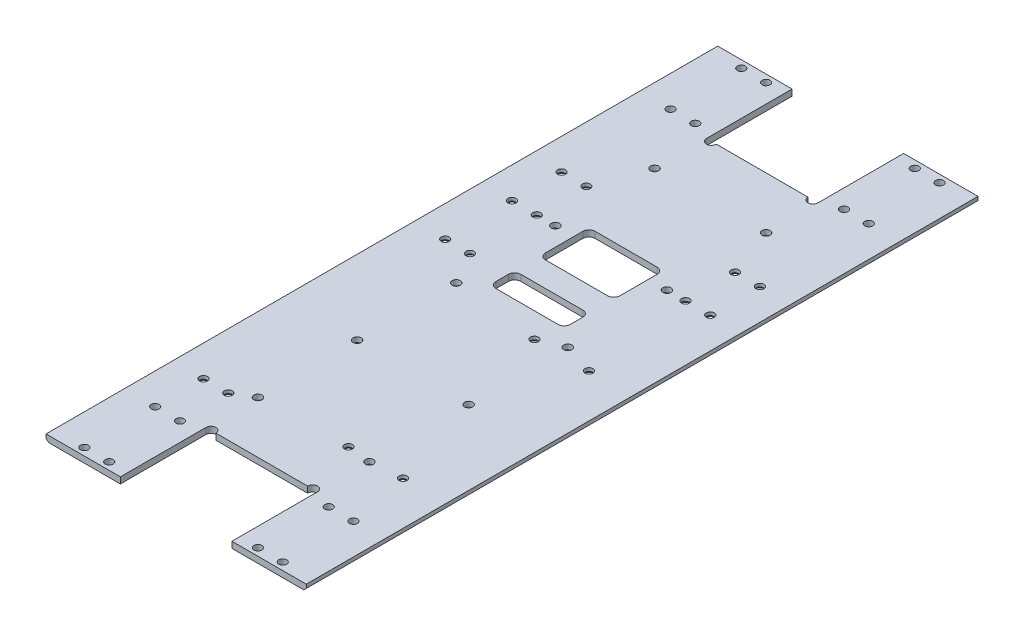
SolidWorks part; units mm, degrees
ref_plane "前视基准面" through (0, 0, 0) normal (0, 0, 1) x (1, 0, 0)
ref_plane "上视基准面" through (0, 0, 0) normal (0, 1, 0) x (1, 0, 0)
ref_plane "右视基准面" through (0, 0, 0) normal (1, 0, 0) x (0, 0, -1)
sketch "草图1" plane through (0, 0, 0) normal (0, 1, 0) x (1, 0, 0)
  line L6 (-52.5, -135.5) -> (52.5, -135.5)
  line L7 (52.5, -135.5) -> (52.5, 135.5)
  line L8 (-52.5, 135.5) -> (52.5, 135.5)
  line L9 (-52.5, -135.5) -> (-52.5, 135.5)
  point P8 (-50, 0)
extrude "凸台-拉伸1" add sketch "草图1" along normal blind 2.5
sketch "草图2" plane through (0, 2.5, 0) normal (0, 1, 0) x (1, 0, 0)
  circle A20 centre (13, -3.95) radius 1.6
  circle A21 centre (35, -3.95) radius 1.6
  circle A24 centre (35, -78.95) radius 1.6
  circle A25 centre (13, -78.95) radius 1.6
extrude "切除-拉伸1" cut sketch "草图2" against normal blind 10
chamfer "倒角4" distance 1 angle 45 2 edges at (52.5, 0, 0) (-52.5, 0, 0)
sketch "草图3" plane through (0, 0, 0) normal (0, -1, 0) x (1, 0, 0)
  line L0 (-22.5, 100.95) -> (22.5, 100.95)
  line L2 (-51.5, 135.5) -> (51.5, 135.5) construction
  line L3 (1.375, 0) -> (-1.375, 0) construction
  line L4 (22.5, 100.95) -> (22.5, 135.5)
  line L5 (22.5, 135.5) -> (-22.5, 135.5)
  line L6 (-22.5, 135.5) -> (-22.5, 100.95)
  line L7 (-22.5, -135.5) -> (-22.5, -100.95)
  line L8 (22.5, -135.5) -> (-22.5, -135.5)
  line L9 (22.5, -100.95) -> (22.5, -135.5)
  line L10 (-22.5, -100.95) -> (22.5, -100.95)
extrude "切除-拉伸2" cut sketch "草图3" against normal blind 10
sketch "草图4" plane through (0, 0, 0) normal (0, -1, 0) x (1, 0, 0)
  line L0 (0, -1.375) -> (0, 1.375) construction
  line L1 (22.5, -100.95) -> (-22.5, -100.95) construction
  line L2 (1.375, 0) -> (-1.375, 0) construction
  circle A0 centre (20.5, -100.95) radius 2
  circle A1 centre (-20.5, -100.95) radius 2
  circle A2 centre (-20.5, 100.95) radius 2
  circle A3 centre (20.5, 100.95) radius 2
extrude "切除-拉伸3" cut sketch "草图4" against normal blind 10
sketch "草图5" plane through (0, 2.5, 0) normal (0, 1, 0) x (1, 0, 0)
  line L0 (0, -1.375) -> (0, 1.375) construction
  line L3 (-1.375, 0) -> (1.375, 0) construction
  circle A0 centre (-40, 103.95) radius 1.6
  circle A1 centre (-30, 103.95) radius 1.6
  circle A4 centre (-40, 132.5) radius 1.6
  circle A5 centre (-30, 132.5) radius 1.6
  circle A6 centre (30, 132.5) radius 1.6
  circle A7 centre (40, 132.5) radius 1.6
  circle A8 centre (30, 103.95) radius 1.6
  circle A9 centre (40, 103.95) radius 1.6
  circle A10 centre (40, -103.95) radius 1.6
  circle A11 centre (30, -103.95) radius 1.6
  circle A12 centre (40, -132.5) radius 1.6
  circle A13 centre (30, -132.5) radius 1.6
  circle A14 centre (-30, -132.5) radius 1.6
  circle A15 centre (-40, -132.5) radius 1.6
  circle A16 centre (-30, -103.95) radius 1.6
  circle A17 centre (-40, -103.95) radius 1.6
extrude "切除-拉伸4" cut sketch "草图5" against normal blind 10
sketch "草图6" plane through (0, 2.5, 0) normal (0, 1, 0) x (1, 0, 0)
  line L0 (0, -1.375) -> (0, 1.375) construction
  circle A0 centre (40, 60) radius 1.6
  circle A1 centre (30, 60) radius 1.6
  circle A2 centre (40, 40) radius 1.6
  circle A3 centre (30, 40) radius 1.6
  circle A4 centre (-30, 40) radius 1.6
  circle A5 centre (-40, 40) radius 1.6
  circle A6 centre (-30, 60) radius 1.6
  circle A7 centre (-40, 60) radius 1.6
  circle A8 centre (-30, -84.45) radius 1.6
  circle A9 centre (-40, -84.45) radius 1.6
  circle A10 centre (-30, 13.05) radius 1.6
  circle A11 centre (-40, 13.05) radius 1.6
  dimension "D1" = 2
extrude "切除-拉伸5" cut sketch "草图6" against normal blind 10
sketch "草图7" plane through (0, 2.5, 0) normal (0, 1, 0) x (1, 0, 0)
  line L0 (0, -1.375) -> (0, 1.375) construction
  line L2 (-1.375, 0) -> (1.375, 0) construction
  circle A0 centre (-22.5, 0) radius 1.65
  circle A2 centre (-22.5, -40) radius 1.65
  circle A4 centre (-22.5, -80) radius 1.65
  circle A5 centre (-22.5, -20) radius 1.65 [skipped]
  circle A6 centre (-22.5, -60) radius 1.65 [skipped]
  circle A7 centre (22.5, -80) radius 1.65
  circle A8 centre (22.5, -40) radius 1.65
  circle A9 centre (22.5, 0) radius 1.65
  circle A10 centre (22.5, 40) radius 1.65
  circle A11 centre (22.5, 80) radius 1.65
  circle A12 centre (-22.5, 80) radius 1.65
  circle A13 centre (-22.5, 40) radius 1.65
  dimension "D1" = 5
extrude "切除-拉伸6" cut sketch "草图7" against normal blind 2
sketch "草图8" plane through (0, 2.5, 0) normal (0, 1, 0) x (1, 0, 0)
  line L0 (0, -1.375) -> (0, 1.375) construction
  circle A0 centre (-22.5, 80) radius 1.55
  circle A1 centre (-22.5, 40) radius 1.55
  circle A2 centre (-22.5, 0) radius 1.55
  circle A3 centre (-22.5, -40) radius 1.55
  circle A4 centre (-22.5, -80) radius 1.55
  circle A5 centre (22.5, -80) radius 1.55
  circle A6 centre (22.5, -40) radius 1.55
  circle A7 centre (22.5, 0) radius 1.55
  circle A8 centre (22.5, 40) radius 1.55
  circle A9 centre (22.5, 80) radius 1.55
  dimension "D1" = 5
extrude "切除-拉伸7" cut sketch "草图8" against normal up to next
chamfer "倒角6" distance 1.2 angle 45 16 edges at (40, 0, -61.6) (30, 0, -61.6) (40, 0, -41.6) (30, 0, -41.6) (-30, 0, -61.6) (-40, 0, -61.6) (-30, 0, -41.6) (-40, 0, -41.6) (-30, 0, 82.85) (-40, 0, 82.85) (-30, 0, -14.65) (-40, 0, -14.65) (35, 0, 2.35) (13, 0, 2.35) (35, 0, 77.35) (13, 0, 77.35)
sketch "草图9" plane through (0, 0, 0) normal (0, -1, 0) x (1, 0, 0)
  line L0 (-15, -26.05) -> (-15, -46.05)
  line L1 (-15, -16.05) -> (15, -16.05)
  line L3 (15, -6.05) -> (-15, -6.05)
  line L4 (-15, -6.05) -> (-15, -16.05)
  line L5 (15, -6.05) -> (15, -16.05)
  line L6 (-15, -46.05) -> (15, -46.05)
  line L8 (15, -26.05) -> (-15, -26.05)
  line L11 (15, -46.05) -> (15, -26.05)
  line L13 (-15, -36.05) -> (15, -36.05) [skipped]
  line L14 (-15, -26.05) -> (-15, -36.05) [skipped]
  line L15 (15, -26.05) -> (15, -36.05) [skipped]
  dimension "D1" = 2
extrude "切除-拉伸8" cut sketch "草图9" against normal blind 12 contours L5 L3 L4 L1 | L11 L8 L0 L6 region at (0, 0, -11.05)
fillet "圆角1" radius 2.5 8 edges at (15, 1.25, -16.05) (15, 1.25, -6.05) (-15, 1.25, -16.05) (-15, 1.25, -6.05) (-15, 1.25, -46.05) (15, 1.25, -46.05) (15, 1.25, -26.05) (-15, 1.25, -26.05)
